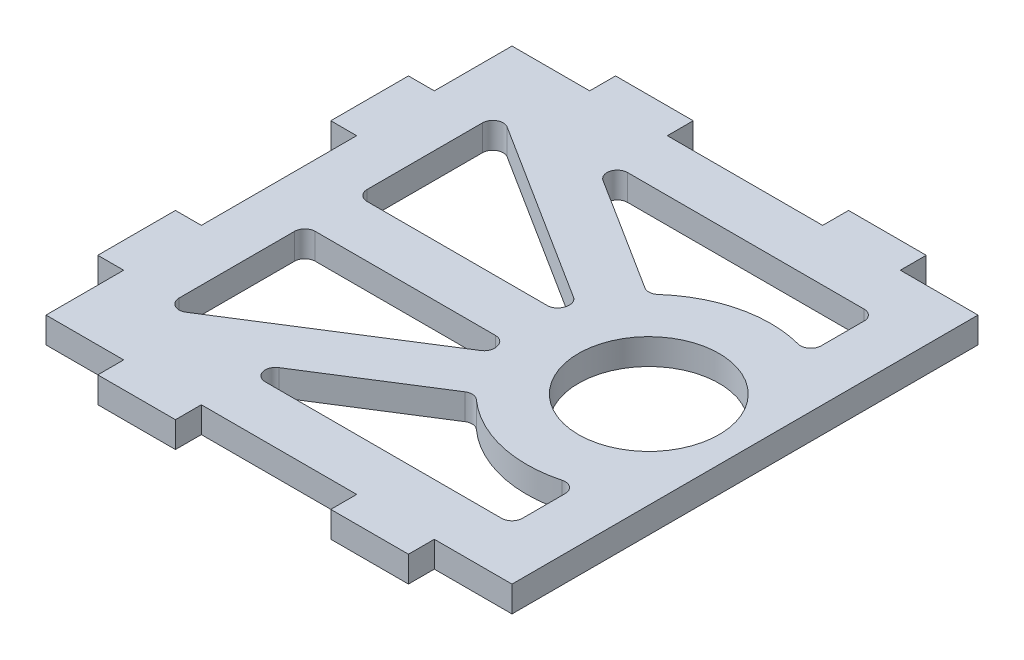
SolidWorks part; units mm, degrees
ref_plane "Front Plane" through (0, 0, 0) normal (0, 0, 1) x (1, 0, 0)
ref_plane "Top Plane" through (0, 0, 0) normal (0, 1, 0) x (1, 0, 0)
ref_plane "Right Plane" through (0, 0, 0) normal (1, 0, 0) x (0, 0, -1)
sketch "Sketch1" plane through (0, 0, 0) normal (0, 1, 0) x (1, 0, 0)
  line L0 (0, 57.15) -> (184.6638, 57.15) construction
  line L1 (0, 0) -> (19.05, 0)
  line L2 (0, 0) -> (0, 19.05)
  line L3 (0, 114.3) -> (19.05, 114.3)
  line L4 (114.3, 0) -> (114.3, 114.3)
  line L5 (38.1, 0) -> (76.2, 0)
  line L7 (95.25, 0) -> (95.25, -6.35)
  line L8 (95.25, -6.35) -> (76.2, -6.35)
  line L9 (76.2, 0) -> (76.2, -6.35)
  line L11 (19.05, 0) -> (19.05, -6.35)
  line L12 (19.05, -6.35) -> (38.1, -6.35)
  line L13 (38.1, 0) -> (38.1, -6.35)
  line L14 (95.25, 0) -> (114.3, 0)
  line L15 (38.1, 114.3) -> (38.1, 120.65)
  line L16 (19.05, 120.65) -> (38.1, 120.65)
  line L17 (19.05, 114.3) -> (19.05, 120.65)
  line L18 (76.2, 114.3) -> (76.2, 120.65)
  line L19 (95.25, 120.65) -> (76.2, 120.65)
  line L20 (95.25, 114.3) -> (95.25, 120.65)
  line L21 (38.1, 114.3) -> (76.2, 114.3)
  line L23 (95.25, 114.3) -> (114.3, 114.3)
  line L24 (-6.35, 19.05) -> (-6.35, 38.1)
  line L25 (0, 95.25) -> (-6.35, 95.25)
  line L27 (0, 76.2) -> (-6.35, 76.2)
  line L28 (-6.35, 95.25) -> (-6.35, 76.2)
  line L29 (0, 38.1) -> (-6.35, 38.1)
  line L31 (0, 19.05) -> (-6.35, 19.05)
  line L32 (0, 95.25) -> (0, 114.3)
  line L33 (0, 38.1) -> (0, 76.2)
  dimension "D1" = 114.3
  dimension "D2" = 114.3
  dimension "D3" = 19.05
  dimension "D4" = 19.05
  dimension "D5" = 19.05
  dimension "D6" = 19.05
  dimension "D7" = 6.35
  dimension "D8" = 6.35
  dimension "D9" = 19.05
  dimension "D10" = 19.05
extrude "Boss-Extrude1" add sketch "Sketch1" against normal blind 6.35
sketch "Sketch2" plane through (0, 0, 0) normal (0, 1, 0) x (1, 0, 0)
  line L0 (114.3, 57.15) -> (55.59, 57.15) construction
  line L1 (114.3, 0) -> (114.3, 114.3) construction
  line L2 (107.95, 57.15) -> (107.95, 78.6846) construction
  circle A0 centre (90.7, 57.15) radius 17.25
  point P8 (0, 0)
  dimension "D1" = 34.5001
  dimension "D2" = 6.35
extrude "Cut-Extrude1" cut sketch "Sketch2" against normal through all
sketch "Sketch3" plane through (0, 0, 0) normal (0, 1, 0) x (1, 0, 0)
  line L0 (90.7, 57.15) -> (-12.2602, 122.2732) construction
  line L1 (87.3056, 51.7834) -> (-15.6546, 116.9066)
  line L2 (94.0944, 62.5166) -> (-8.8658, 127.6398)
  line L3 (90.7, 57.15) -> (22.3264, 57.15) construction
  line L4 (90.7, 57.15) -> (-12.2602, -7.9732) construction
  line L5 (87.3056, 62.5166) -> (-15.6546, -2.6066)
  line L6 (94.0944, 51.7834) -> (-8.8658, -13.3398)
  line L35 (90.7, 57.15) -> (-12.2602, 57.15) construction
  line L36 (90.7, 50.8) -> (-12.2602, 50.8)
  line L37 (90.7, 63.5) -> (-12.2602, 63.5)
  line L63 (12.7, 12.7) -> (101.6, 12.7)
  line L64 (101.6, 12.7) -> (101.6, 101.6)
  line L65 (101.6, 101.6) -> (12.7, 101.6)
  line L66 (12.7, 101.6) -> (12.7, 12.7)
  line L67 (12.7, 12.7) -> (101.6, 12.7)
  line L68 (101.6, 12.7) -> (101.6, 101.6)
  line L69 (101.6, 101.6) -> (12.7, 101.6)
  line L70 (12.7, 101.6) -> (12.7, 12.7)
  arc A0 (87.3056, 51.7834) -> (94.0944, 62.5166) centre (90.7, 57.15) ccw
  arc A1 (-8.8658, 127.6398) -> (-15.6546, 116.9066) centre (-12.2602, 122.2732) ccw
  arc A3 (87.3056, 62.5166) -> (94.0944, 51.7834) centre (90.7, 57.15) cw
  circle A4 centre (90.7, 57.15) radius 29.95
  circle A5 centre (90.7, 57.15) radius 29.95
  arc A6 (-8.8658, -13.3398) -> (-15.6546, -2.6066) centre (-12.2602, -7.9732) cw
  arc A7 (90.7, 50.8) -> (90.7, 63.5) centre (90.7, 57.15) ccw
  arc A8 (-12.2602, 63.5) -> (-12.2602, 50.8) centre (-12.2602, 57.15) ccw
  point P2 (39.2199, 89.7116)
  point P8 (39.2199, 24.5884)
  point P19 (39.2199, 57.15)
  dimension "D2" = 6.35
  dimension "D1" = 12.7
  dimension "D3" = 12.7
extrude "Cut-Extrude2" cut sketch "Sketch3" against normal through all contours A5 L68 L69 L2 | A5 L1 L70 L37 | A5 L36 L70 L5 | A5 L6 L67 L68 region at (30.9036, 0, -75.4809) region at (30.9036, 0, -38.8191) region at (72.1425, 0, -20.8641) region at (72.1425, 0, -93.4359)
fillet "Fillet1" radius 2.54 16 edges at (61.4308, -3.175, -63.5) (12.7, -3.175, -63.5) (62.5692, -3.175, -67.4293) (101.6, -3.175, -29.2539) (101.6, -3.175, -12.7) (32.3033, -3.175, -12.7) (69.3581, -3.175, -36.1375) (69.3581, -3.175, -78.1625) (32.3033, -3.175, -101.6) (101.6, -3.175, -101.6) (101.6, -3.175, -85.0461) (62.5692, -3.175, -46.8707) (12.7, -3.175, -15.328) (12.7, -3.175, -50.8) (61.4308, -3.175, -50.8) (12.7, -3.175, -98.972)
